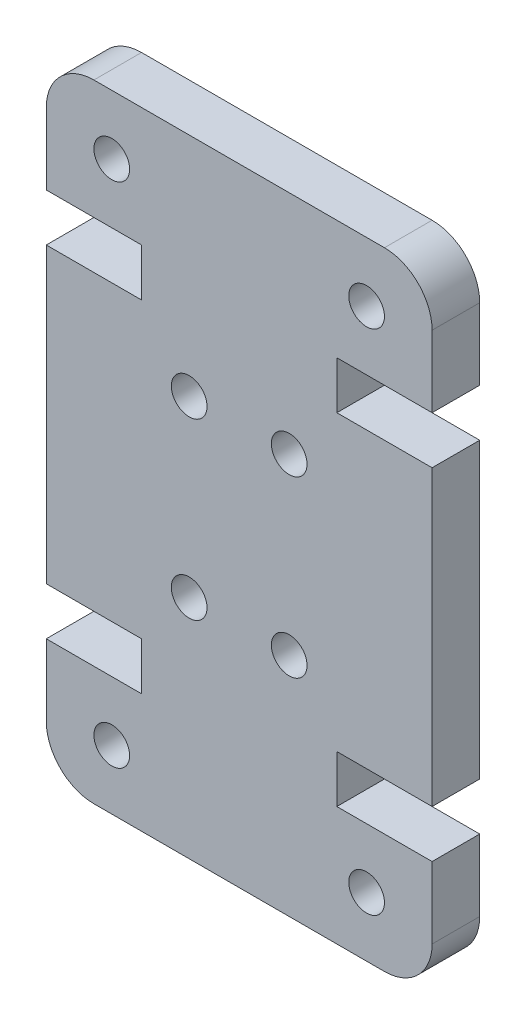
SolidWorks part; units mm, degrees
ref_plane "Front Plane" through (0, 0, 0) normal (0, 0, 1) x (1, 0, 0)
ref_plane "Top Plane" through (0, 0, 0) normal (0, 1, 0) x (1, 0, 0)
ref_plane "Right Plane" through (0, 0, 0) normal (1, 0, 0) x (0, 0, -1)
sketch "Sketch2" plane through (0, 0, 0) normal (0, 0, 1) x (1, 0, 0)
  line L20 (0, 19.32) -> (0, 7)
  line L21 (16.2, 19.32) -> (16.2, 7)
  line L22 (2, 26.32) -> (14.2, 26.32)
  line L23 (2, 0) -> (14.2, 0)
  line L24 (4, 21.32) -> (4, 19.32)
  line L25 (0, 21.32) -> (4, 21.32)
  line L26 (4, 19.32) -> (0, 19.32)
  line L27 (4, 7) -> (4, 5)
  line L28 (0, 24.32) -> (0, 21.32)
  line L29 (16.2, 21.32) -> (16.2, 24.32)
  line L30 (0, 7) -> (4, 7)
  line L31 (12.2, 21.32) -> (12.2, 19.32)
  line L32 (4, 5) -> (0, 5)
  line L33 (12.2, 19.32) -> (16.2, 19.32)
  line L34 (16.2, 21.32) -> (12.2, 21.32)
  line L35 (12.2, 7) -> (12.2, 5)
  line L36 (0, 2) -> (0, 5)
  line L37 (16.2, 5) -> (16.2, 2)
  line L38 (12.2, 5) -> (16.2, 5)
  line L39 (16.2, 7) -> (12.2, 7)
  arc A12 (16.2, 24.32) -> (14.2, 26.32) centre (14.2, 24.32) ccw
  arc A13 (2, 26.32) -> (0, 24.32) centre (2, 24.32) ccw
  circle A14 centre (10.2, 16.82) radius 0.75
  circle A15 centre (6, 16.82) radius 0.75
  arc A16 (14.2, 0) -> (16.2, 2) centre (14.2, 2) ccw
  arc A17 (0, 2) -> (2, 0) centre (2, 2) ccw
  circle A18 centre (10.2, 9.5) radius 0.75
  circle A19 centre (6, 9.5) radius 0.75
  circle A20 centre (13.45, 2.5) radius 0.75
  circle A21 centre (2.75, 2.5) radius 0.75
  circle A22 centre (13.45, 23.82) radius 0.75
  circle A23 centre (2.75, 23.82) radius 0.75
extrude "Boss-Extrude1" add sketch "Sketch2" along normal blind 2
